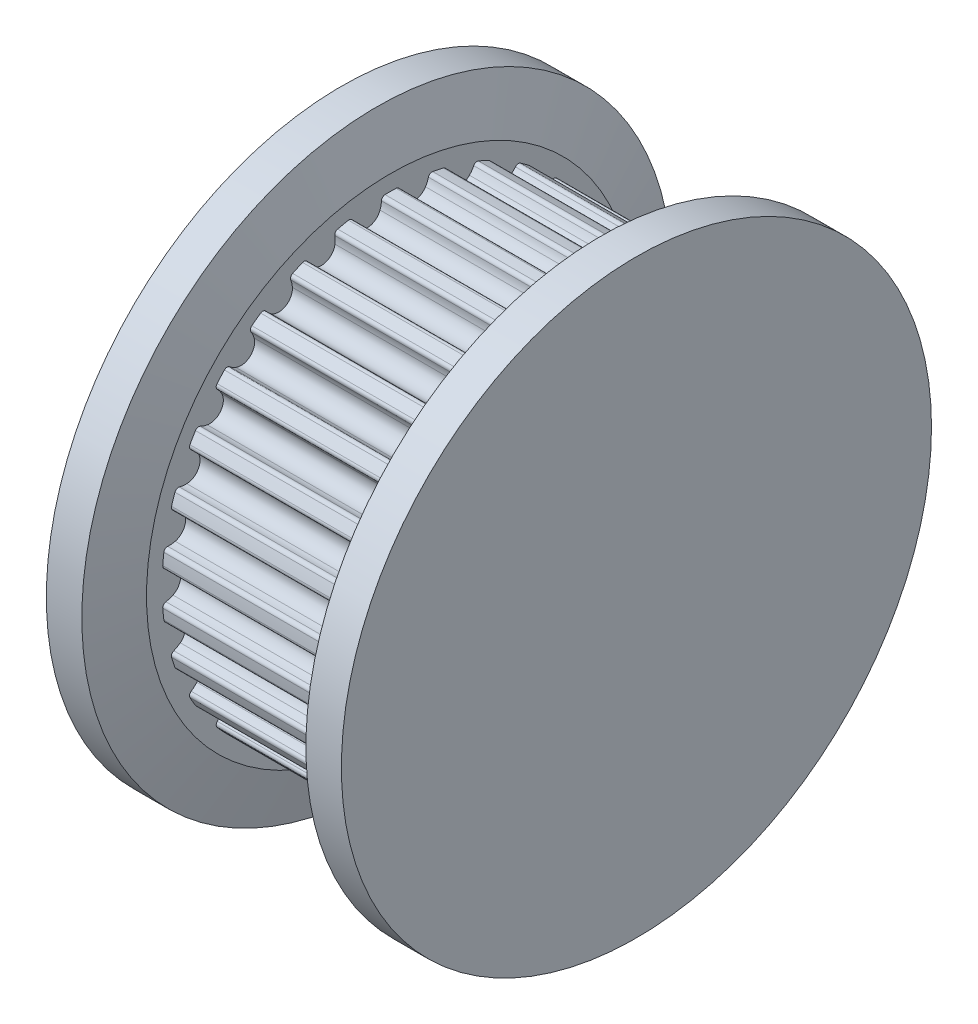
SolidWorks part; units mm, degrees
ref_plane "Front Plane" through (0, 0, 0) normal (0, 0, 1) x (1, 0, 0)
ref_plane "Top Plane" through (0, 0, 0) normal (0, 1, 0) x (1, 0, 0)
ref_plane "Right Plane" through (0, 0, 0) normal (1, 0, 0) x (0, 0, -1)
sketch "Teeth" plane through (0, 0, 0) normal (1, 0, 0) x (0, 0, -1)
  line L0 (0, 0) -> (9.7637, 0) construction
  line L1 (0, 0) -> (9.497, 0.9982) construction
  line L2 (0, 0) -> (9.497, -0.9982) construction
  arc A0 (9.265, -0.7494) -> (9.2444, -0.9716) centre (0, 0) cw
  arc A1 (8.8479, 0.4987) -> (9.1379, 0.589) centre (9.2867, -0.3999) cw
  arc A2 (8.8479, -0.4987) -> (9.1379, -0.589) centre (9.2867, 0.3999) ccw
  arc A3 (9.1379, -0.589) -> (9.265, -0.7494) centre (9.1155, -0.7373) cw
  arc A4 (8.9068, -2.6593) -> (8.8404, -2.8724) centre (0, 0) cw
  arc A5 (8.8157, -2.476) -> (8.9068, -2.6593) centre (8.763, -2.6164) cw
  arc A6 (8.8479, 0.4987) -> (8.8479, -0.4987) centre (9.0914, 0) ccw
  arc A7 (8.5509, -2.3274) -> (8.8157, -2.476) centre (9.1669, -1.5397) ccw
  arc A8 (8.7583, -1.3518) -> (8.5509, -2.3274) centre (8.8928, -1.8902) ccw
  arc A9 (8.7583, -1.3518) -> (9.0606, -1.3238) centre (9.0006, -2.322) cw
  arc A10 (9.0606, -1.3238) -> (9.2184, -1.1933) centre (9.0696, -1.174) ccw
  arc A11 (9.2184, -1.1933) -> (9.2444, -0.9716) centre (0, 0) ccw
  arc A12 (8.1592, -4.453) -> (8.05, -4.6476) centre (0, 0) cw
  arc A13 (8.1083, -4.2548) -> (8.1592, -4.453) centre (8.0276, -4.3812) cw
  arc A14 (7.8801, -4.0544) -> (8.1083, -4.2548) centre (8.6465, -3.4119) ccw
  circle A15 centre (0, 0) radius 9.5493 construction
  circle A16 centre (0, 0) radius 9.2953 construction
  arc A17 (8.2858, -3.1432) -> (7.8801, -4.0544) centre (8.3054, -3.6978) ccw
  arc A18 (8.2858, -3.1432) -> (8.5874, -3.1786) centre (8.3212, -4.1425) cw
  arc A19 (8.5874, -3.1786) -> (8.7688, -3.0838) centre (8.6273, -3.034) ccw
  arc A20 (8.7688, -3.0838) -> (8.8404, -2.8724) centre (0, 0) ccw
  arc A21 (7.0551, -6.0521) -> (6.9078, -6.2198) centre (0, 0) cw
  arc A22 (7.0465, -5.8476) -> (7.0551, -6.0521) centre (6.9412, -5.9545) cw
  circle A23 centre (0, 0) radius 9.9253 construction
  arc A24 (6.865, -5.6042) -> (7.0465, -5.8476) centre (7.7481, -5.1351) ccw
  arc A25 (7.4513, -4.7972) -> (6.865, -5.6042) centre (7.3551, -5.3438) ccw
  arc A26 (7.4513, -4.7972) -> (7.7389, -4.8946) centre (7.278, -5.7821) cw
  arc A27 (7.7389, -4.8946) -> (7.9361, -4.8396) centre (7.808, -4.7615) ccw
  arc A28 (7.9361, -4.8396) -> (8.05, -4.6476) centre (0, 0) ccw
  arc A29 (5.6426, -7.3867) -> (5.4636, -7.5201) centre (0, 0) cw
  arc A30 (5.6767, -7.1849) -> (5.6426, -7.3867) centre (5.5515, -7.2675) cw
  arc A31 (5.5498, -6.909) -> (5.6767, -7.1849) centre (6.5112, -6.6338) ccw
  arc A32 (6.291, -6.2416) -> (5.5498, -6.909) centre (6.0834, -6.7563) ccw
  arc A33 (6.291, -6.2416) -> (6.5521, -6.3966) centre (5.9168, -7.1689) cw
  arc A34 (6.5521, -6.3966) -> (6.7564, -6.3838) centre (6.6474, -6.2808) ccw
  arc A35 (6.7564, -6.3838) -> (6.9078, -6.2198) centre (0, 0) ccw
  arc A36 (3.9835, -8.3985) -> (3.7807, -8.4917) centre (0, 0) cw
  arc A37 (4.0589, -8.2081) -> (3.9835, -8.3985) centre (3.9192, -8.2629) cw
  arc A38 (3.9921, -7.9119) -> (4.0589, -8.2081) centre (4.9896, -7.8426) ccw
  arc A39 (4.8559, -7.4132) -> (3.9921, -7.9119) centre (4.5457, -7.8734) ccw
  arc A40 (4.8559, -7.4132) -> (5.079, -7.6191) centre (4.297, -8.2424) cw
  arc A41 (5.079, -7.6191) -> (5.2815, -7.6491) centre (5.1963, -7.5256) ccw
  arc A42 (5.2815, -7.6491) -> (5.4636, -7.5201) centre (0, 0) ccw
  arc A43 (2.1503, -9.0432) -> (1.9326, -9.0922) centre (0, 0) cw
  arc A44 (2.2636, -8.8726) -> (2.1503, -9.0432) centre (2.1156, -8.8972) cw
  arc A45 (2.2598, -8.569) -> (2.2636, -8.8726) centre (3.2501, -8.7086) ccw
  arc A46 (3.2085, -8.2608) -> (2.2598, -8.569) centre (2.8094, -8.6465) ccw
  arc A47 (3.2085, -8.2608) -> (3.3839, -8.5086) centre (2.4894, -8.9557) cw
  arc A48 (3.3839, -8.5086) -> (3.5758, -8.58) centre (3.5181, -8.4415) ccw
  arc A49 (3.5758, -8.58) -> (3.7807, -8.4917) centre (0, 0) ccw
  arc A50 (0.2232, -9.2926) -> (0, -9.2953) centre (0, 0) cw
  arc A51 (0.3694, -9.1494) -> (0.2232, -9.2926) centre (0.2196, -9.1427) cw
  arc A52 (0.4289, -8.8516) -> (0.3694, -9.1494) centre (1.3684, -9.194) ccw
  arc A53 (1.4208, -8.7473) -> (0.4289, -8.8516) centre (0.9503, -9.0416) ccw
  arc A54 (1.4208, -8.7473) -> (1.5409, -9.0262) centre (0.573, -9.2776) cw
  arc A55 (1.5409, -9.0262) -> (1.7138, -9.1359) centre (1.6861, -8.9885) ccw
  arc A56 (1.7138, -9.1359) -> (1.9326, -9.0922) centre (0, 0) ccw
  arc A57 (-1.7138, -9.1359) -> (-1.9326, -9.0922) centre (0, 0) cw
  arc A58 (-1.5409, -9.0262) -> (-1.7138, -9.1359) centre (-1.6861, -8.9885) cw
  arc A59 (-1.4208, -8.7473) -> (-1.5409, -9.0262) centre (-0.573, -9.2776) ccw
  arc A60 (-0.4289, -8.8516) -> (-1.4208, -8.7473) centre (-0.9503, -9.0416) ccw
  arc A61 (-0.4289, -8.8516) -> (-0.3694, -9.1494) centre (-1.3684, -9.194) cw
  arc A62 (-0.3694, -9.1494) -> (-0.2232, -9.2926) centre (-0.2196, -9.1427) ccw
  arc A63 (9.265, 0.7494) -> (9.2444, 0.9716) centre (0, 0) ccw
  arc A64 (-0.2232, -9.2926) -> (0, -9.2953) centre (0, 0) ccw
  arc A65 (9.1379, 0.589) -> (9.265, 0.7494) centre (9.1155, 0.7373) ccw
  arc A66 (-3.5758, -8.58) -> (-3.7807, -8.4917) centre (0, 0) cw
  arc A67 (-3.3839, -8.5086) -> (-3.5758, -8.58) centre (-3.5181, -8.4415) cw
  arc A68 (-3.2085, -8.2608) -> (-3.3839, -8.5086) centre (-2.4894, -8.9557) ccw
  arc A69 (-2.2598, -8.569) -> (-3.2085, -8.2608) centre (-2.8094, -8.6465) ccw
  arc A70 (-2.2598, -8.569) -> (-2.2636, -8.8726) centre (-3.2501, -8.7086) cw
  arc A71 (-2.2636, -8.8726) -> (-2.1503, -9.0432) centre (-2.1156, -8.8972) ccw
  arc A72 (-2.1503, -9.0432) -> (-1.9326, -9.0922) centre (0, 0) ccw
  arc A73 (-5.2815, -7.6491) -> (-5.4636, -7.5201) centre (0, 0) cw
  arc A74 (-5.079, -7.6191) -> (-5.2815, -7.6491) centre (-5.1963, -7.5256) cw
  arc A75 (-4.8559, -7.4132) -> (-5.079, -7.6191) centre (-4.297, -8.2424) ccw
  arc A76 (-3.9921, -7.9119) -> (-4.8559, -7.4132) centre (-4.5457, -7.8734) ccw
  arc A77 (-3.9921, -7.9119) -> (-4.0589, -8.2081) centre (-4.9896, -7.8426) cw
  arc A78 (-4.0589, -8.2081) -> (-3.9835, -8.3985) centre (-3.9192, -8.2629) ccw
  arc A79 (-3.9835, -8.3985) -> (-3.7807, -8.4917) centre (0, 0) ccw
  arc A80 (-6.7564, -6.3838) -> (-6.9078, -6.2198) centre (0, 0) cw
  arc A81 (-6.5521, -6.3966) -> (-6.7564, -6.3838) centre (-6.6474, -6.2808) cw
  arc A82 (-6.291, -6.2416) -> (-6.5521, -6.3966) centre (-5.9168, -7.1689) ccw
  arc A83 (-5.5498, -6.909) -> (-6.291, -6.2416) centre (-6.0834, -6.7563) ccw
  arc A84 (-5.5498, -6.909) -> (-5.6767, -7.1849) centre (-6.5112, -6.6338) cw
  arc A85 (-5.6767, -7.1849) -> (-5.6426, -7.3867) centre (-5.5515, -7.2675) ccw
  arc A86 (-5.6426, -7.3867) -> (-5.4636, -7.5201) centre (0, 0) ccw
  arc A87 (-7.9361, -4.8396) -> (-8.05, -4.6476) centre (0, 0) cw
  arc A88 (-7.7389, -4.8946) -> (-7.9361, -4.8396) centre (-7.808, -4.7615) cw
  arc A89 (-7.4513, -4.7972) -> (-7.7389, -4.8946) centre (-7.278, -5.7821) ccw
  arc A90 (-6.865, -5.6042) -> (-7.4513, -4.7972) centre (-7.3551, -5.3438) ccw
  arc A91 (-6.865, -5.6042) -> (-7.0465, -5.8476) centre (-7.7481, -5.1351) cw
  arc A92 (-7.0465, -5.8476) -> (-7.0551, -6.0521) centre (-6.9412, -5.9545) ccw
  arc A93 (-7.0551, -6.0521) -> (-6.9078, -6.2198) centre (0, 0) ccw
  arc A94 (-8.7688, -3.0838) -> (-8.8404, -2.8724) centre (0, 0) cw
  arc A95 (-8.5874, -3.1786) -> (-8.7688, -3.0838) centre (-8.6273, -3.034) cw
  arc A96 (-8.2858, -3.1432) -> (-8.5874, -3.1786) centre (-8.3212, -4.1425) ccw
  arc A97 (-7.8801, -4.0544) -> (-8.2858, -3.1432) centre (-8.3054, -3.6978) ccw
  arc A98 (-7.8801, -4.0544) -> (-8.1083, -4.2548) centre (-8.6465, -3.4119) cw
  arc A99 (-8.1083, -4.2548) -> (-8.1592, -4.453) centre (-8.0276, -4.3812) ccw
  arc A100 (-8.1592, -4.453) -> (-8.05, -4.6476) centre (0, 0) ccw
  arc A101 (-9.2184, -1.1933) -> (-9.2444, -0.9716) centre (0, 0) cw
  arc A102 (-9.0606, -1.3238) -> (-9.2184, -1.1933) centre (-9.0696, -1.174) cw
  arc A103 (-8.7583, -1.3518) -> (-9.0606, -1.3238) centre (-9.0006, -2.322) ccw
  arc A104 (-8.5509, -2.3274) -> (-8.7583, -1.3518) centre (-8.8928, -1.8902) ccw
  arc A105 (-8.5509, -2.3274) -> (-8.8157, -2.476) centre (-9.1669, -1.5397) cw
  arc A106 (-8.8157, -2.476) -> (-8.9068, -2.6593) centre (-8.763, -2.6164) ccw
  arc A107 (-8.9068, -2.6593) -> (-8.8404, -2.8724) centre (0, 0) ccw
  arc A108 (-9.265, 0.7494) -> (-9.2444, 0.9716) centre (0, 0) cw
  arc A109 (-9.1379, 0.589) -> (-9.265, 0.7494) centre (-9.1155, 0.7373) cw
  arc A110 (-8.8479, 0.4987) -> (-9.1379, 0.589) centre (-9.2867, -0.3999) ccw
  arc A111 (-8.8479, -0.4987) -> (-8.8479, 0.4987) centre (-9.0914, 0) ccw
  arc A112 (-8.8479, -0.4987) -> (-9.1379, -0.589) centre (-9.2867, 0.3999) cw
  arc A113 (-9.1379, -0.589) -> (-9.265, -0.7494) centre (-9.1155, -0.7373) ccw
  arc A114 (-9.265, -0.7494) -> (-9.2444, -0.9716) centre (0, 0) ccw
  arc A115 (-8.9068, 2.6593) -> (-8.8404, 2.8724) centre (0, 0) cw
  arc A116 (-8.8157, 2.476) -> (-8.9068, 2.6593) centre (-8.763, 2.6164) cw
  arc A117 (-8.5509, 2.3274) -> (-8.8157, 2.476) centre (-9.1669, 1.5397) ccw
  arc A118 (-8.7583, 1.3518) -> (-8.5509, 2.3274) centre (-8.8928, 1.8902) ccw
  arc A119 (-8.7583, 1.3518) -> (-9.0606, 1.3238) centre (-9.0006, 2.322) cw
  arc A120 (-9.0606, 1.3238) -> (-9.2184, 1.1933) centre (-9.0696, 1.174) ccw
  arc A121 (-9.2184, 1.1933) -> (-9.2444, 0.9716) centre (0, 0) ccw
  arc A122 (-8.1592, 4.453) -> (-8.05, 4.6476) centre (0, 0) cw
  arc A123 (-8.1083, 4.2548) -> (-8.1592, 4.453) centre (-8.0276, 4.3812) cw
  arc A124 (-7.8801, 4.0544) -> (-8.1083, 4.2548) centre (-8.6465, 3.4119) ccw
  arc A125 (-8.2858, 3.1432) -> (-7.8801, 4.0544) centre (-8.3054, 3.6978) ccw
  arc A126 (-8.2858, 3.1432) -> (-8.5874, 3.1786) centre (-8.3212, 4.1425) cw
  arc A127 (-8.5874, 3.1786) -> (-8.7688, 3.0838) centre (-8.6273, 3.034) ccw
  arc A128 (-8.7688, 3.0838) -> (-8.8404, 2.8724) centre (0, 0) ccw
  arc A129 (-7.0551, 6.0521) -> (-6.9078, 6.2198) centre (0, 0) cw
  arc A130 (-7.0465, 5.8476) -> (-7.0551, 6.0521) centre (-6.9412, 5.9545) cw
  arc A131 (-6.865, 5.6042) -> (-7.0465, 5.8476) centre (-7.7481, 5.1351) ccw
  arc A132 (-7.4513, 4.7972) -> (-6.865, 5.6042) centre (-7.3551, 5.3438) ccw
  arc A133 (-7.4513, 4.7972) -> (-7.7389, 4.8946) centre (-7.278, 5.7821) cw
  arc A134 (-7.7389, 4.8946) -> (-7.9361, 4.8396) centre (-7.808, 4.7615) ccw
  arc A135 (-7.9361, 4.8396) -> (-8.05, 4.6476) centre (0, 0) ccw
  arc A136 (-5.6426, 7.3867) -> (-5.4636, 7.5201) centre (0, 0) cw
  arc A137 (-5.6767, 7.1849) -> (-5.6426, 7.3867) centre (-5.5515, 7.2675) cw
  arc A138 (-5.5498, 6.909) -> (-5.6767, 7.1849) centre (-6.5112, 6.6338) ccw
  arc A139 (-6.291, 6.2416) -> (-5.5498, 6.909) centre (-6.0834, 6.7563) ccw
  arc A140 (-6.291, 6.2416) -> (-6.5521, 6.3966) centre (-5.9168, 7.1689) cw
  arc A141 (-6.5521, 6.3966) -> (-6.7564, 6.3838) centre (-6.6474, 6.2808) ccw
  arc A142 (-6.7564, 6.3838) -> (-6.9078, 6.2198) centre (0, 0) ccw
  arc A143 (-3.9835, 8.3985) -> (-3.7807, 8.4917) centre (0, 0) cw
  arc A144 (-4.0589, 8.2081) -> (-3.9835, 8.3985) centre (-3.9192, 8.2629) cw
  arc A145 (-3.9921, 7.9119) -> (-4.0589, 8.2081) centre (-4.9896, 7.8426) ccw
  arc A146 (-4.8559, 7.4132) -> (-3.9921, 7.9119) centre (-4.5457, 7.8734) ccw
  arc A147 (-4.8559, 7.4132) -> (-5.079, 7.6191) centre (-4.297, 8.2424) cw
  arc A148 (-5.079, 7.6191) -> (-5.2815, 7.6491) centre (-5.1963, 7.5256) ccw
  arc A149 (-5.2815, 7.6491) -> (-5.4636, 7.5201) centre (0, 0) ccw
  arc A150 (-2.1503, 9.0432) -> (-1.9326, 9.0922) centre (0, 0) cw
  arc A151 (-2.2636, 8.8726) -> (-2.1503, 9.0432) centre (-2.1156, 8.8972) cw
  arc A152 (-2.2598, 8.569) -> (-2.2636, 8.8726) centre (-3.2501, 8.7086) ccw
  arc A153 (-3.2085, 8.2608) -> (-2.2598, 8.569) centre (-2.8094, 8.6465) ccw
  arc A154 (-3.2085, 8.2608) -> (-3.3839, 8.5086) centre (-2.4894, 8.9557) cw
  arc A155 (-3.3839, 8.5086) -> (-3.5758, 8.58) centre (-3.5181, 8.4415) ccw
  arc A156 (-3.5758, 8.58) -> (-3.7807, 8.4917) centre (0, 0) ccw
  arc A157 (-0.2232, 9.2926) -> (0, 9.2953) centre (0, 0) cw
  arc A158 (-0.3694, 9.1494) -> (-0.2232, 9.2926) centre (-0.2196, 9.1427) cw
  arc A159 (-0.4289, 8.8516) -> (-0.3694, 9.1494) centre (-1.3684, 9.194) ccw
  arc A160 (-1.4208, 8.7473) -> (-0.4289, 8.8516) centre (-0.9503, 9.0416) ccw
  arc A161 (-1.4208, 8.7473) -> (-1.5409, 9.0262) centre (-0.573, 9.2776) cw
  arc A162 (-1.5409, 9.0262) -> (-1.7138, 9.1359) centre (-1.6861, 8.9885) ccw
  arc A163 (-1.7138, 9.1359) -> (-1.9326, 9.0922) centre (0, 0) ccw
  arc A164 (1.7138, 9.1359) -> (1.9326, 9.0922) centre (0, 0) cw
  arc A165 (1.5409, 9.0262) -> (1.7138, 9.1359) centre (1.6861, 8.9885) cw
  arc A166 (1.4208, 8.7473) -> (1.5409, 9.0262) centre (0.573, 9.2776) ccw
  arc A167 (0.4289, 8.8516) -> (1.4208, 8.7473) centre (0.9503, 9.0416) ccw
  arc A168 (0.4289, 8.8516) -> (0.3694, 9.1494) centre (1.3684, 9.194) cw
  arc A169 (0.3694, 9.1494) -> (0.2232, 9.2926) centre (0.2196, 9.1427) ccw
  arc A170 (0.2232, 9.2926) -> (0, 9.2953) centre (0, 0) ccw
  arc A171 (3.5758, 8.58) -> (3.7807, 8.4917) centre (0, 0) cw
  arc A172 (3.3839, 8.5086) -> (3.5758, 8.58) centre (3.5181, 8.4415) cw
  arc A173 (3.2085, 8.2608) -> (3.3839, 8.5086) centre (2.4894, 8.9557) ccw
  arc A174 (2.2598, 8.569) -> (3.2085, 8.2608) centre (2.8094, 8.6465) ccw
  arc A175 (2.2598, 8.569) -> (2.2636, 8.8726) centre (3.2501, 8.7086) cw
  arc A176 (2.2636, 8.8726) -> (2.1503, 9.0432) centre (2.1156, 8.8972) ccw
  arc A177 (2.1503, 9.0432) -> (1.9326, 9.0922) centre (0, 0) ccw
  arc A178 (5.2815, 7.6491) -> (5.4636, 7.5201) centre (0, 0) cw
  arc A179 (5.079, 7.6191) -> (5.2815, 7.6491) centre (5.1963, 7.5256) cw
  arc A180 (4.8559, 7.4132) -> (5.079, 7.6191) centre (4.297, 8.2424) ccw
  arc A181 (3.9921, 7.9119) -> (4.8559, 7.4132) centre (4.5457, 7.8734) ccw
  arc A182 (3.9921, 7.9119) -> (4.0589, 8.2081) centre (4.9896, 7.8426) cw
  arc A183 (4.0589, 8.2081) -> (3.9835, 8.3985) centre (3.9192, 8.2629) ccw
  arc A184 (3.9835, 8.3985) -> (3.7807, 8.4917) centre (0, 0) ccw
  arc A185 (6.7564, 6.3838) -> (6.9078, 6.2198) centre (0, 0) cw
  arc A186 (6.5521, 6.3966) -> (6.7564, 6.3838) centre (6.6474, 6.2808) cw
  arc A187 (6.291, 6.2416) -> (6.5521, 6.3966) centre (5.9168, 7.1689) ccw
  arc A188 (5.5498, 6.909) -> (6.291, 6.2416) centre (6.0834, 6.7563) ccw
  arc A189 (5.5498, 6.909) -> (5.6767, 7.1849) centre (6.5112, 6.6338) cw
  arc A190 (5.6767, 7.1849) -> (5.6426, 7.3867) centre (5.5515, 7.2675) ccw
  arc A191 (5.6426, 7.3867) -> (5.4636, 7.5201) centre (0, 0) ccw
  arc A192 (7.9361, 4.8396) -> (8.05, 4.6476) centre (0, 0) cw
  arc A193 (7.7389, 4.8946) -> (7.9361, 4.8396) centre (7.808, 4.7615) cw
  arc A194 (7.4513, 4.7972) -> (7.7389, 4.8946) centre (7.278, 5.7821) ccw
  arc A195 (6.865, 5.6042) -> (7.4513, 4.7972) centre (7.3551, 5.3438) ccw
  arc A196 (6.865, 5.6042) -> (7.0465, 5.8476) centre (7.7481, 5.1351) cw
  arc A197 (7.0465, 5.8476) -> (7.0551, 6.0521) centre (6.9412, 5.9545) ccw
  arc A198 (7.0551, 6.0521) -> (6.9078, 6.2198) centre (0, 0) ccw
  arc A199 (8.7688, 3.0838) -> (8.8404, 2.8724) centre (0, 0) cw
  arc A200 (8.5874, 3.1786) -> (8.7688, 3.0838) centre (8.6273, 3.034) cw
  arc A201 (8.2858, 3.1432) -> (8.5874, 3.1786) centre (8.3212, 4.1425) ccw
  arc A202 (7.8801, 4.0544) -> (8.2858, 3.1432) centre (8.3054, 3.6978) ccw
  arc A203 (7.8801, 4.0544) -> (8.1083, 4.2548) centre (8.6465, 3.4119) cw
  arc A204 (8.1083, 4.2548) -> (8.1592, 4.453) centre (8.0276, 4.3812) ccw
  arc A205 (8.1592, 4.453) -> (8.05, 4.6476) centre (0, 0) ccw
  arc A206 (9.2184, 1.1933) -> (9.2444, 0.9716) centre (0, 0) cw
  arc A207 (9.0606, 1.3238) -> (9.2184, 1.1933) centre (9.0696, 1.174) cw
  arc A208 (8.7583, 1.3518) -> (9.0606, 1.3238) centre (9.0006, 2.322) ccw
  arc A209 (8.5509, 2.3274) -> (8.7583, 1.3518) centre (8.8928, 1.8902) ccw
  arc A210 (8.5509, 2.3274) -> (8.8157, 2.476) centre (9.1669, 1.5397) cw
  arc A211 (8.8157, 2.476) -> (8.9068, 2.6593) centre (8.763, 2.6164) ccw
  arc A212 (8.9068, 2.6593) -> (8.8404, 2.8724) centre (0, 0) ccw
  point P2 (8.5364, 0)
  point P4 (9.5493, 0)
  point P45 (0, 0)
  point P48 (6.05, 0)
  point P53 (9.2953, 0)
  point P175 (0, 0)
  point P178 (9.2759, 0.6001)
  point P297 (0, 0)
  dimension "D1" = 0.63
  dimension "D2" = 1
  dimension "D3" = 0.4
  dimension "D5" = 2
  dimension "D6" = 0.254
  dimension "D8" = 30
  dimension "D4" = 0.555
  dimension "D7" = 0.15
extrude "Boss-Extrude1" add sketch "Teeth" along normal mid plane 8
sketch "Sketch3" plane through (0, 0, 0) normal (0, 0, 1) x (1, 0, 0)
  line L0 (4, 0) -> (-4, 0) construction
  line L1 (-4, 0) -> (-4, 9.9253)
  line L2 (-4, 0) -> (-6, 0)
  line L3 (-4, 9.9253) -> (-4.5559, 12)
  line L4 (-4.5559, 12) -> (-6, 12)
  line L5 (0, 0) -> (0, 9.9253) construction
  line L6 (-4, 9.9253) -> (4, 9.9253) construction
  line L7 (4, 0) -> (6, 0)
  line L8 (4, 9.9253) -> (4.5559, 12)
  line L9 (-6, 0) -> (-6, 12)
  line L10 (4.5559, 12) -> (6, 12)
  line L11 (6, 0) -> (6, 12)
  line L12 (4, 0) -> (4, 9.9253)
  point P5 (0, 0)
  dimension "D1" = 8
  dimension "D2" = 2
  dimension "D3" = 12
  dimension "D4" = 15
revolve "Revolve1" add sketch "Sketch3" angle 360 about L0
ref_axis "Axis" through (6.6, 0, 0) along (-1, 0, 0)
